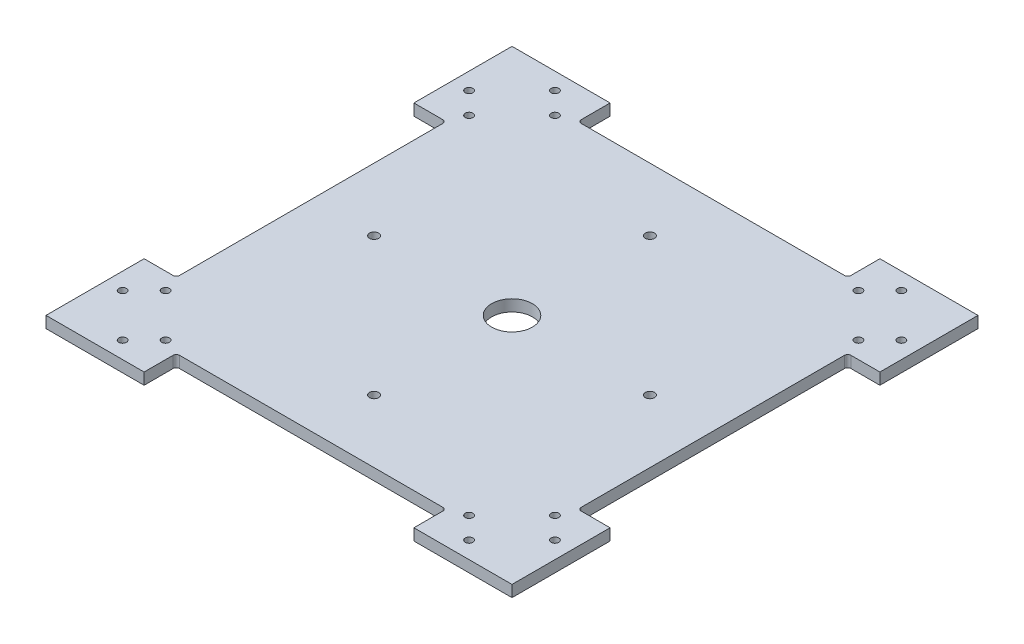
SolidWorks part; units mm, degrees
note: '?' marks a value the reader was unsure of.
material "Pine"
ref_plane "Front Plane" through (0, 0, 0) normal (0, 0, 1) x (1, 0, 0)
ref_plane "Top Plane" through (0, 0, 0) normal (0, 1, 0) x (1, 0, 0)
ref_plane "Right Plane" through (0, 0, 0) normal (1, 0, 0) x (0, 0, -1)
ref_axis "Axis1" through (0, -18.3356, 0) along (0, 1, 0)?
sketch "Sketch1" plane through (0, 0, 0) normal (0, 1, 0) x (1, 0, 0)
  line L1 (-241.3, 241.3) -> (241.3, 241.3) construction
  line L2 (-241.3, 241.3) -> (-241.3, -241.3) construction
  line L3 (-241.3, -241.3) -> (241.3, -241.3) construction
  line L4 (241.3, 241.3) -> (241.3, -241.3) construction
  line L5 (0, -241.3) -> (0, 241.3) construction
  line L6 (-241.3, 0) -> (241.3, 0) construction
  line L7 (-207.9625, 207.9625) -> (207.9625, 207.9625) construction
  line L8 (-207.9625, 207.9625) -> (-207.9625, -207.9625) construction
  line L9 (-207.9625, -207.9625) -> (207.9625, -207.9625) construction
  line L10 (207.9625, 207.9625) -> (207.9625, -207.9625) construction
  line L11 (0, -207.9625) -> (0, 207.9625) construction
  line L12 (-207.9625, 0) -> (207.9625, 0) construction
  line L13 (-241.3, 241.3) -> (-139.7, 241.3) construction
  line L14 (-241.3, 241.3) -> (-241.3, 139.7) construction
  line L15 (-241.3, 139.7) -> (-139.7, 139.7) construction
  line L16 (-139.7, 241.3) -> (-139.7, 139.7) construction
  line L17 (241.3, 241.3) -> (139.7, 241.3) construction
  line L18 (241.3, 241.3) -> (241.3, 139.7) construction
  line L19 (241.3, 139.7) -> (139.7, 139.7) construction
  line L20 (139.7, 241.3) -> (139.7, 139.7) construction
  line L21 (241.3, -241.3) -> (139.7, -241.3) construction
  line L22 (241.3, -241.3) -> (241.3, -139.7) construction
  line L23 (241.3, -139.7) -> (139.7, -139.7) construction
  line L24 (139.7, -241.3) -> (139.7, -139.7) construction
  line L25 (-241.3, -241.3) -> (-139.7, -241.3) construction
  line L26 (-241.3, -241.3) -> (-241.3, -139.7) construction
  line L27 (-241.3, -139.7) -> (-139.7, -139.7) construction
  line L28 (-139.7, -241.3) -> (-139.7, -139.7) construction
  point P0 (0, 0)
  point P4 (0, 0)
  dimension "D1" = 482.6
  dimension "D2" = 415.925
  dimension "D3" = 101.6
  dimension "D4" = 279.4
sketch "Sketch2" plane through (0, 0, 0) normal (0, 1, 0) x (1, 0, 0)
  line L0 (-241.3, 241.3) -> (-139.7, 241.3)
  line L1 (-139.7, 241.3) -> (-139.7, 207.9625)
  line L2 (-207.9625, 207.9625) -> (207.9625, 207.9625) construction
  line L3 (-139.7, 241.3) -> (-139.7, 139.7) construction
  line L4 (-139.7, 207.9625) -> (139.7, 207.9625)
  line L5 (139.7, 241.3) -> (139.7, 139.7) construction
  line L6 (139.7, 207.9625) -> (139.7, 241.3)
  line L7 (139.7, 241.3) -> (241.3, 241.3)
  line L8 (241.3, 241.3) -> (241.3, 139.7)
  line L9 (241.3, 139.7) -> (207.9625, 139.7)
  line L10 (207.9625, 207.9625) -> (207.9625, -207.9625) construction
  line L11 (207.9625, 139.7) -> (207.9625, -139.7)
  line L12 (241.3, -139.7) -> (139.7, -139.7) construction
  line L13 (207.9625, -139.7) -> (241.3, -139.7)
  line L14 (241.3, -139.7) -> (241.3, -241.3)
  line L15 (241.3, -241.3) -> (139.7, -241.3)
  line L16 (-241.3, -241.3) -> (241.3, -241.3) construction
  line L17 (139.7, -241.3) -> (139.7, -207.9625)
  line L18 (-207.9625, -207.9625) -> (207.9625, -207.9625) construction
  line L19 (139.7, -241.3) -> (139.7, -139.7) construction
  line L20 (139.7, -207.9625) -> (-139.7, -207.9625)
  line L21 (-139.7, -207.9625) -> (-139.7, -241.3)
  line L22 (-139.7, -241.3) -> (-241.3, -241.3)
  line L23 (-241.3, -241.3) -> (-241.3, -139.7)
  line L24 (-241.3, -139.7) -> (-207.9625, -139.7)
  line L25 (-207.9625, 207.9625) -> (-207.9625, -207.9625) construction
  line L26 (-241.3, -139.7) -> (-139.7, -139.7) construction
  line L27 (-207.9625, -139.7) -> (-207.9625, 139.7)
  line L28 (-241.3, 139.7) -> (-139.7, 139.7) construction
  line L29 (-207.9625, 139.7) -> (-241.3, 139.7)
  line L30 (-241.3, 139.7) -> (-241.3, 241.3)
extrude "Boss-Extrude1" add sketch "Sketch2" against normal blind 11.9062
fillet "Fillet1" radius 3.3782 8 edges at (-207.9625, -5.9531, -139.7) (-207.9625, -5.9531, 139.7) (139.7, -5.9531, 207.9625) (207.9625, -5.9531, 139.7) (207.9625, -5.9531, -139.7) (139.7, -5.9531, -207.9625) (-139.7, -5.9531, -207.9625) (-139.7, -5.9531, 207.9625)
sketch "Sketch6" plane through (0, -11.9062, 0) normal (0, -1, 0) x (1, 0, 0)
  line L0 (0, 142.875) -> (-142.875, 0) construction
  line L1 (0, 241.3) -> (0, -241.3) construction
  line L2 (-241.3, 0) -> (241.3, 0) construction
  line L3 (-142.875, 0) -> (0, -142.875) construction
  line L4 (0, -142.875) -> (142.875, 0) construction
  line L5 (142.875, 0) -> (0, 142.875) construction
  dimension "D1" = 285.75
hole_wizard "for connection to donut" positions "Sketch7" profile "Sketch8" hole size "3/8" standard "ANSI Inch" end condition up to next
sketch "Sketch7" plane through (0, -11.9062, 0) normal (0, -1, 0) x (-1, 0, 0)
  point P0 (0, -142.875)
  point P3 (142.875, 0)
  point P6 (0, 142.875)
  point P9 (-142.875, 0)
sketch "Sketch8" plane through (0, -11.9062, 142.875) normal (1, 0, 0) x (0, 0, -1)
  line L0 (0, 0) -> (0, 11.9062)
  line L1 (0, 11.9062) -> (4.7625, 11.9062)
  line L2 (4.7625, 11.9062) -> (4.7625, 0)
  line L5 (4.7625, 0) -> (0, 0)
  line L11 (0, -6.35) -> (0, 107.95) construction
  dimension "Thru Hole Dia." = 9.525
  dimension "Thru Hole Depth" = 11.9062
sketch "Sketch11" plane through (0, -11.9062, 0) normal (0, -1, 0) x (-1, 0, 0)
  line L2 (-241.3, 241.3) -> (-139.7, 241.3) construction
  line L3 (-241.3, 139.7) -> (-241.3, 241.3) construction
  line L4 (-223.8375, 179.3875) -> (-201.6125, 157.1625) construction
  line L6 (-179.3875, 223.8375) -> (-157.1625, 201.6125) construction
  point P0 (-201.6125, 157.1625)
  point P1 (-223.8375, 179.3875)
  point P2 (-179.3875, 223.8375)
  point P3 (-157.1625, 201.6125)
  dimension "D1" = 17.4625
  dimension "D2" = 39.6875
  dimension "D3" = 61.9125
  dimension "D4" = 84.1375
  dimension "D5" = 17.4625
  dimension "D6" = 39.6875
  dimension "D7" = 61.9125
  dimension "D8" = 84.1375
  dimension "D9" = 31.4309
hole_wizard "5/16 (0.3125) Diameter Hole1" positions "Sketch12" profile "Sketch13" hole size "5/16" standard "ANSI Inch" end condition up to next
sketch "Sketch12" plane through (0, -11.9062, 0) normal (0, -1, 0) x (-1, 0, 0)
  point P0 (-157.1625, 201.6125)
  point P3 (-179.3875, 223.8375)
  point P6 (-223.8375, 179.3875)
  point P9 (-201.6125, 157.1625)
sketch "Sketch13" plane through (157.1625, -11.9062, -201.6125) normal (1, 0, 0) x (0, 0, -1)
  line L0 (0, 0) -> (0, 11.9072)
  line L1 (0, 11.9072) -> (3.9687, 11.9072)
  line L2 (3.9687, 11.9072) -> (3.9687, 0)
  line L5 (3.9687, 0) -> (0, 0)
  line L11 (0, -6.35) -> (0, 107.95) construction
  dimension "Thru Hole Dia." = 7.9375
  dimension "Thru Hole Depth" = 11.9072
pattern_circular "CirPattern1" count 4 over 360 about axis through (0, 0, 0) along (0, 1, 0) of "5/16 (0.3125) Diameter Hole1"
sketch "Sketch3" [suppressed] plane through (0, 0, 0) normal (0, 1, 0) x (1, 0, 0)
  line L0 (-22.225, 49.2125) -> (-107.95, -44.45)
  line L1 (-107.95, -44.45) -> (-44.45, -107.95)
  line L2 (-44.45, -107.95) -> (49.2125, -22.225)
  line L3 (49.2125, -22.225) -> (-22.225, 49.2125)
  line L4 (0, -241.3) -> (0, 241.3) construction
  line L5 (-241.3, 0) -> (241.3, 0) construction
  dimension "D1" = 22.225
  dimension "D2" = 49.2125
  dimension "D3" = 44.45
  dimension "D4" = 107.95
  dimension "D5" = 22.225
  dimension "D6" = 49.2125
  dimension "D7" = 44.45
  dimension "D8" = 107.95
hole_wizard "for agitator" [suppressed] positions "Sketch4" profile "Sketch5" hole size "3/8" standard "ANSI Inch"
sketch "Sketch4" [suppressed] plane through (0, 0, 0) normal (0, 1, 0) x (1, 0, 0)
  point P0 (-22.225, 49.2125)
  point P3 (-107.95, -44.45)
  point P6 (-44.45, -107.95)
  point P9 (49.2125, -22.225)
sketch "Sketch5" plane through (-22.225, 0, -49.2125) normal (1, 0, 0) x (0, 0, 1)
  line L0 (0, 0) -> (0, 18.2562)
  line L1 (0, 18.2562) -> (4.7625, 18.2562)
  line L2 (4.7625, 18.2562) -> (4.7625, 0)
  line L5 (4.7625, 0) -> (0, 0)
  line L11 (0, -6.35) -> (0, 107.95) construction
  dimension "Thru Hole Dia." = 9.525
  dimension "Thru Hole Depth" = 18.2562
sketch "Sketch9" [suppressed] plane through (0, -17.4625, 0) normal (0, -1, 0) x (1, 0, 0)
  line L0 (-124.5466, 69.85) -> (15.1534, -63.5)
  line L1 (15.1534, -63.5) -> (66.675, -9.525)
  line L2 (66.675, -9.525) -> (-73.025, 123.825)
  line L3 (-73.025, 123.825) -> (-124.5466, 69.85)
  line L4 (-241.3, 0) -> (241.3, 0) construction
  line L5 (0, 241.3) -> (0, -241.3) construction
  dimension "D1" = 9.525
  dimension "D2" = 123.825
  dimension "D3" = 73.025
  dimension "D4" = 66.675
  dimension "D5" = 69.85
sketch "Sketch14" plane through (0, 0, 0) normal (0, 1, 0) x (1, 0, 0)
  circle A0 centre (0, 0) radius 21.082
  dimension "D1" = 42.164
extrude "hole for wheel on a stick" cut sketch "Sketch14" against normal through all
sketch "Sketch15" [suppressed] plane through (0, 0, 0) normal (0, 1, 0) x (1, 0, 0)
  line L0 (-47.625, -1.5875) -> (-1.5875, -47.625)
  line L1 (-1.5875, -47.625) -> (42.0688, -3.9688)
  line L2 (42.0688, -3.9688) -> (49.2125, -11.1125)
  line L3 (49.2125, -11.1125) -> (74.6125, 14.2875)
  line L4 (74.6125, 14.2875) -> (67.4688, 21.4312)
  line L5 (67.4688, 21.4312) -> (122.2375, 76.2)
  line L6 (122.2375, 76.2) -> (76.2, 122.2375)
  line L7 (99.2188, 99.2187) -> (-24.6063, -24.6062) construction
  line L8 (-207.9625, 136.3218) -> (-207.9625, -136.3218) construction
  line L9 (-136.3218, -207.9625) -> (136.3218, -207.9625) construction
  line L10 (207.9625, -136.3218) -> (207.9625, 136.3218) construction
  line L11 (21.4313, 67.4688) -> (76.2, 122.2375)
  line L12 (14.2875, 74.6125) -> (21.4313, 67.4688)
  line L13 (-11.1125, 49.2125) -> (14.2875, 74.6125)
  line L14 (-3.9687, 42.0688) -> (-11.1125, 49.2125)
  line L15 (-47.625, -1.5875) -> (-3.9687, 42.0688)
  dimension "D1" = 206.375
  dimension "D2" = 160.3375
  dimension "D3" = 196.85
  dimension "D4" = 222.25
  dimension "D5" = 45
  dimension "D6" = 257.175
  dimension "D7" = 85.725
extrude "Cutout-Motorized" [suppressed] cut sketch "Sketch15" against normal through all
fillet "Fillet2" [suppressed] radius 3.3782
sketch "Sketch16" [suppressed] plane through (0, 0, 0) normal (0, 1, 0) x (1, 0, 0)
  line L0 (-47.625, -1.5875) -> (-1.5875, -47.625)
  line L1 (-1.5875, -47.625) -> (42.0688, -3.9688)
  line L2 (42.0688, -3.9688) -> (49.2125, -11.1125)
  line L3 (49.2125, -11.1125) -> (74.6125, 14.2875)
  line L4 (74.6125, 14.2875) -> (14.2875, 74.6125)
  line L5 (44.45, 44.45) -> (-24.6063, -24.6062) construction
  line L6 (-136.3218, -207.9625) -> (136.3218, -207.9625) construction
  line L7 (-207.9625, 136.3218) -> (-207.9625, -136.3218) construction
  line L8 (-11.1125, 49.2125) -> (14.2875, 74.6125)
  line L9 (-3.9687, 42.0688) -> (-11.1125, 49.2125)
  line L10 (-47.625, -1.5875) -> (-3.9687, 42.0688)
  dimension "D1" = 45
  dimension "D2" = 160.3375
  dimension "D3" = 206.375
  dimension "D4" = 222.25
  dimension "D5" = 196.85
  dimension "D6" = 257.175
extrude "Cutout-NoMotor" [suppressed] cut sketch "Sketch16" against normal through all
fillet "Fillet3" [suppressed] radius 3.3782
